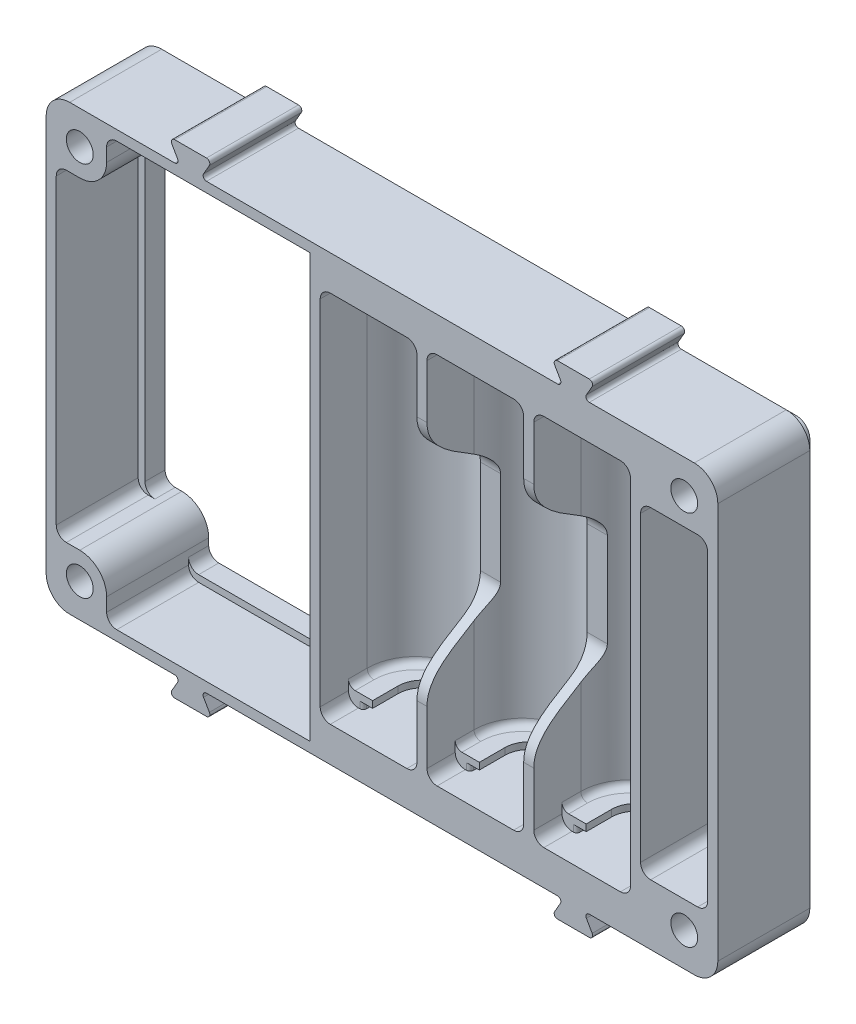
SolidWorks part; units mm, degrees
material "ABS"
ref_plane "Front Plane" through (0, 0, 0) normal (0, 0, 1) x (1, 0, 0)
ref_plane "Top Plane" through (0, 0, 0) normal (0, 1, 0) x (1, 0, 0)
ref_plane "Right Plane" through (0, 0, 0) normal (1, 0, 0) x (0, 0, -1)
sketch "Sketch1" plane through (0, 0, 0) normal (0, 1, 0) x (1, 0, 0)
  line L0 (-24.6, 0) -> (24.6, 0)
  line L1 (0, 0) -> (0, -8.2) construction
  line L2 (-5.4908, -1) -> (5.6475, -1) construction
  line L3 (7, -12.213) -> (7, -2.6204) construction
  line L4 (8.9, -12.0066) -> (8.9, -2.0587) construction
  line L5 (0, -8.2) -> (15.9, -8.2) construction
  line L6 (7.2, -8.2) -> (7.2, -15.2)
  line L7 (8.7, -8.2) -> (8.7, -15.2)
  line L8 (8.7, -15.2) -> (23.1, -15.2) construction
  line L9 (8.7, -15.2) -> (7.2, -15.2)
  line L10 (-1.7094, -15.2) -> (7.2, -15.2) construction
  line L11 (15.9, -8.2) -> (23.1, -8.2) construction
  line L12 (23.1, -15.2) -> (23.1, -8.2)
  line L13 (23.1, -15.2) -> (24.6, -15.2)
  line L14 (24.6, -15.2) -> (24.6, 0)
  line L15 (-24.6, -15.2) -> (-24.6, 0)
  line L16 (-23.1, -15.2) -> (-24.6, -15.2)
  line L17 (-23.1, -15.2) -> (-23.1, -8.2)
  line L18 (-8.7, -8.2) -> (-8.7, -15.2)
  line L19 (-8.7, -15.2) -> (-7.2, -15.2)
  line L20 (-7.2, -8.2) -> (-7.2, -15.2)
  circle A0 centre (0, -8.2) radius 7 construction
  arc A1 (-7.2, -8.2) -> (7.2, -8.2) centre (0, -8.2) cw
  circle A2 centre (15.9, -8.2) radius 7 construction
  arc A3 (8.7, -8.2) -> (23.1, -8.2) centre (15.9, -8.2) cw
  arc A4 (-8.7, -8.2) -> (-23.1, -8.2) centre (-15.9, -8.2) ccw
  dimension "D1" = 14
  dimension "D2" = 0.2
  dimension "D3" = 1
  dimension "D4" = 1.5
  dimension "D5" = 15.2
  dimension "D6" = 15.9
extrude "Boss-Extrude1" add sketch "Sketch1" along normal blind 27.8
sketch "Sketch2" plane through (0, 27.8, 0) normal (0, -1, 0) x (1, 0, 0)
  line L1 (-24.6, 15.2) -> (24.6, 15.2)
  line L2 (-24.6, 15.2) -> (-24.6, 0)
  line L3 (-24.6, 0) -> (24.6, 0)
  line L4 (24.6, 15.2) -> (24.6, 0)
extrude "Boss-Extrude2" add sketch "Sketch2" against normal blind 1.5
ref_plane "Plane1" through (-15.9, 0, 0) normal (1, 0, 0) x (0, 0, -1)
ref_plane "Plane3" through (15.9, 0, 0) normal (1, 0, 0) x (0, 0, -1)
sketch "Sketch6" plane through (0, 0, 0) normal (1, 0, 0) x (0, 0, -1)
  line L0 (-5, 0) -> (-15.2, 0)
  line L1 (-15.2, 0) -> (0, 0) construction
  line L2 (-15.2, 0) -> (-15.2, 18.3)
  line L3 (-15.2, 29.3) -> (-15.2, 0) construction
  line L4 (-5, 0) -> (-5, 7)
  line L5 (0, 29.3) -> (0, 0) construction
  line L6 (0, 29.3) -> (-15.2, 29.3) construction
  spline S0 degree 3 poles (-15.2, 18.3) (-15.2, 12.3) (-5, 11) (-5, 7) knots 0 0 0 0 1 1 1 1
  dimension "D4" = 12
  dimension "D5" = 18
  dimension "D1" = 7
  dimension "D2" = 5
  dimension "D3" = 11
extrude "Cut-Extrude2" cut sketch "Sketch6" against normal blind 15 and the other way blind 15
sketch "Sketch3" plane through (0, 27.8, 0) normal (0, -1, 0) x (1, 0, 0)
  line L0 (-10.4, 11) -> (-8.7, 11)
  line L1 (-8.7, 8.2) -> (-8.7, 15.2) construction
  line L2 (-8.7, 11) -> (-8.7, 0)
  line L3 (24.6, 0) -> (-24.6, 0) construction
  line L4 (-8.7, 0) -> (-23.1, 0)
  line L6 (-20.4, 2.9) -> (-11.4, 2.9)
  line L7 (-10.9, 3.4) -> (-10.9, 10.5)
  line L8 (-15.9, 15.2) -> (-15.9, 0) construction
  line L9 (-8.7, 15.2) -> (-23.1, 15.2) construction
  line L19 (-23.1, 11) -> (-23.1, 0)
  line L20 (-21.4, 11) -> (-23.1, 11)
  line L21 (-20.9, 3.4) -> (-20.9, 10.5)
  arc A1 (-11.4, 2.9) -> (-10.9, 3.4) centre (-11.4, 3.4) ccw
  arc A4 (-10.4, 11) -> (-10.9, 10.5) centre (-10.4, 10.5) ccw
  arc A6 (-20.4, 2.9) -> (-20.9, 3.4) centre (-20.4, 3.4) cw
  arc A7 (-21.4, 11) -> (-20.9, 10.5) centre (-21.4, 10.5) cw
  dimension "D6" = 0.5
  dimension "D7" = 0.5
  dimension "D1" = 5
  dimension "D2" = 11
  dimension "D3" = 2.9
extrude "Inner" add sketch "Sketch3" along normal blind 1
sketch "Sketch4" plane through (0, 26.8, 0) normal (0, -1, 0) x (1, 0, 0)
  line L1 (-8.7, 8.2) -> (-8.7, 15.2) construction
  line L2 (-8.7, 11) -> (-8.7, 0)
  line L3 (24.6, 0) -> (-24.6, 0) construction
  line L4 (-8.7, 0) -> (-23.1, 0)
  line L5 (-23.1, 0) -> (-23.1, 11)
  line L6 (-8.7, 11) -> (-10.4, 11) construction
  line L7 (-23.1, 11) -> (-19.5, 11)
  line L8 (-19.5, 11) -> (-19.5, 7.2)
  line L10 (-12.3, 7.2) -> (-12.3, 11)
  line L11 (-12.3, 11) -> (-8.7, 11)
  arc A0 (-19.5, 7.2) -> (-12.3, 7.2) centre (-15.9, 7.2) ccw
  dimension "D1" = 3.6
  dimension "D2" = 3.8
extrude "Boss-Extrude4" add sketch "Sketch4" along normal blind 1
sketch "Sketch5" plane through (0, 0, 15.2) normal (0, 0, 1) x (1, 0, 0)
  line L0 (-8.7, 27.8) -> (-23.1, 27.8) construction
  line L1 (-17.6, 27.8) -> (-14.2, 27.8)
  line L2 (-17.6, 27.8) -> (-17.6, 27.3)
  line L3 (-17.6, 27.3) -> (-14.2, 27.3)
  line L4 (-14.2, 27.8) -> (-14.2, 27.3)
  point P10 (-15.9, 27.8)
  dimension "D1" = 0.5
  dimension "D2" = 3.4
extrude "Cut-Extrude1" cut sketch "Sketch5" against normal through all
sketch "Sketch10" plane through (0, 0, 0) normal (0, 0, 1) x (1, 0, 0)
  line L0 (-24.6, 29.3) -> (24.6, 29.3) construction
  line L1 (-14.2, 27.3) -> (-17.6, 27.3)
  line L2 (-14.2, 27.3) -> (-14.2, 29.3)
  line L3 (-14.2, 29.3) -> (-17.6, 29.3)
  line L4 (-17.6, 27.3) -> (-17.6, 29.3)
extrude "Cut-Extrude6" cut sketch "Sketch10" along normal blind 0.6
mirror "Mirror1" about plane through (0, 0, 0) normal (1, 0, 0) of "Cut-Extrude6", "Inner", "Boss-Extrude4", "Cut-Extrude1"
ref_plane "Plane2" through (-7.95, 0, 0) normal (1, 0, 0) x (0, 0, -1)
mirror "Mirror2" about plane through (-7.95, 0, 0) normal (1, 0, 0) of "Cut-Extrude6", "Inner", "Boss-Extrude4", "Cut-Extrude1"
fillet "Fillet2" radius 1.5 6 edges at (-8.7, 27.8, 13.1) (-23.1, 27.8, 13.1) (8.7, 27.8, 13.1) (23.1, 27.8, 13.1) (7.2, 27.8, 13.1) (-7.2, 27.8, 13.1)
fillet "Fillet3" radius 1 9 edges at (-8.7, 25.8, 9.6) (-15.9, 25.8, 1) (-23.1, 25.8, 9.6) (23.1, 25.8, 9.6) (8.7, 25.8, 9.6) (7.2, 25.8, 9.6) (-7.2, 25.8, 9.6) (15.9, 25.8, 1) (0, 25.8, 1)
mirror "Mirror4" about plane through (0, 0, 0) normal (0, 1, 0) of bodies 108 110
sketch "Эскиз1" plane through (0, 0, 0) normal (0, 0, -1) x (-1, 0, 0)
  line L0 (-24.6, 29.3) -> (-24.6, -29.3) construction
  line L5 (-36.1, 33) -> (63.9, 33)
  line L6 (-36.1, 33) -> (-36.1, -33)
  line L7 (-36.1, -33) -> (63.9, -33)
  line L8 (63.9, 33) -> (63.9, -33)
  line L9 (-36.1, 33) -> (63.9, -33) construction
  line L10 (-36.1, -33) -> (63.9, 33) construction
  line L11 (-34.6, -31.5) -> (62.4, -31.5)
  line L12 (-34.6, -31.5) -> (-34.6, 31.5)
  line L13 (-34.6, 31.5) -> (62.4, 31.5)
  line L14 (62.4, -31.5) -> (62.4, 31.5)
  line L15 (-34.6, -31.5) -> (62.4, 31.5) construction
  line L16 (-34.6, 31.5) -> (62.4, -31.5) construction
  line L17 (24.6, 29.3) -> (24.6, -29.3) construction
  line L18 (-24.6, 29.3) -> (24.6, 29.3)
  line L19 (-24.6, 29.3) -> (-24.6, 31.5)
  line L20 (-24.6, 31.5) -> (24.6, 31.5)
  line L21 (24.6, 29.3) -> (24.6, 31.5)
  line L22 (-24.6, -29.3) -> (24.6, -29.3)
  line L23 (-24.6, -29.3) -> (-24.6, -31.5)
  line L24 (-24.6, -31.5) -> (24.6, -31.5)
  line L25 (24.6, -29.3) -> (24.6, -31.5)
  line L27 (-24.6, 29.3) -> (-24.6, -29.3) construction
  line L28 (62.4, 31.5) -> (54.9, 31.5)
  line L29 (62.4, 31.5) -> (62.4, 24)
  line L30 (62.4, 24) -> (54.9, 24)
  line L31 (54.9, 31.5) -> (54.9, 24)
  line L32 (62.4, -31.5) -> (54.9, -31.5)
  line L33 (62.4, -31.5) -> (62.4, -24)
  line L34 (62.4, -24) -> (54.9, -24)
  line L35 (54.9, -31.5) -> (54.9, -24)
  line L36 (-34.6, 31.5) -> (-24.6, 31.5)
  line L37 (-34.6, 31.5) -> (-34.6, 24)
  line L38 (-34.6, 24) -> (-24.6, 24)
  line L39 (-24.6, 31.5) -> (-24.6, 24)
  line L41 (-34.6, -31.5) -> (-24.6, -31.5)
  line L42 (-34.6, -31.5) -> (-34.6, -24)
  line L43 (-34.6, -24) -> (-24.6, -24)
  line L44 (-24.6, -31.5) -> (-24.6, -24)
  point P0 (13.9, 0)
  point P5 (13.9, 0)
  line M16 (24.6, 29.3) -> (17.6, 29.3)
  line M20 (14.2, 29.3) -> (1.7, 29.3)
  line M24 (-1.7, 29.3) -> (-14.2, 29.3)
  line M28 (-17.6, 29.3) -> (-24.6, 29.3)
  line M30 (-24.6, 29.3) -> (-24.6, -29.3)
  dimension "D1" = 100
  dimension "D2" = 66
  dimension "D3" = 1.5
  dimension "D4" = 1.5
  dimension "D5" = 10
  dimension "D6" = 7.5
extrude "Бобышка-Вытянуть1" add sketch "Эскиз1" against normal up to surface (15.2 mm away) contours L13 L31 L30 L14 | L35 L11 L14 L34 | L43 L12 L11 L23 M30 | L12 L38 L19 L13 M30 | L8 L5 L6 L7 L14 L11 L12 L13 | L21 L13 L19 L18 M16 M28 M24 M20 | L23 L22 L25 L24 region at (-13.9, 31.8018, 0) region at (29.6, -27.75, 0) region at (29.6, 27.75, 0) region at (-58.65, -27.75, 0) region at (0, 30.4, 0) region at (-58.65, 27.75, 0) up to face at (0, 0, 15.2)
sketch "Эскиз2" plane through (0, 0, 0) normal (0, 0, -1) x (-1, 0, 0)
  line L0 (62.4, -24) -> (62.4, 24) construction
  line L1 (-34.6, -31.5) -> (62.4, -31.5)
  line L2 (-34.6, -31.5) -> (-34.6, 31.5)
  line L3 (-34.6, 31.5) -> (62.4, 31.5)
  line L4 (62.4, -31.5) -> (62.4, 31.5)
  line L5 (-34.6, -24) -> (-34.6, 24) construction
  line L6 (24.6, 31.5) -> (54.9, 31.5) construction
  line L7 (24.6, -31.5) -> (54.9, -31.5) construction
  line L8 (-24.6, 24) -> (-24.6, -24) construction
  line L11 (-34.6, 24) -> (-24.6, 24)
  line L12 (-24.6, 31.5) -> (-24.6, 24)
  line L13 (54.9, 24) -> (62.4, 24)
  line L14 (54.9, 24) -> (54.9, 31.5)
  line L17 (54.9, -24) -> (62.4, -24)
  line L18 (54.9, -24) -> (54.9, -31.5)
  line L23 (-34.6, -24) -> (-24.6, -24)
  line L24 (-24.6, -31.5) -> (-24.6, -24)
  line L25 (-24.6, 30.5) -> (54.9, 30.5)
  line L26 (-24.6, -30.5) -> (54.9, -30.5)
  line L27 (-33.6, 24) -> (-33.6, -24)
  line L28 (61.4, -24) -> (61.4, 24)
  line L29 (62.4, 24) -> (54.9, 24) construction
  line M25 (-34.6, 24) -> (-24.6, 24)
  line M27 (-24.6, -24) -> (-34.6, -24)
  line M28 (-34.6, -24) -> (-34.6, 24)
  line M29 (24.6, -31.5) -> (24.6, 31.5)
  line M30 (24.6, 31.5) -> (54.9, 31.5)
  line M31 (54.9, 31.5) -> (54.9, 24)
  line M32 (54.9, 24) -> (62.4, 24)
  line M33 (62.4, 24) -> (62.4, -24)
  line M34 (62.4, -24) -> (54.9, -24)
  line M35 (54.9, -24) -> (54.9, -31.5)
  line M36 (54.9, -31.5) -> (24.6, -31.5)
  dimension "D1" = 1
  dimension "D2" = 1
  dimension "D3" = 1
  dimension "D4" = 1
extrude "Бобышка-Вытянуть2" add sketch "Эскиз2" against normal blind 3 contours L12 L3 L2 L11 M25 | L12 L25 L3 M29 | L25 M29 M31 M30 | L13 L4 L3 L14 M32 M31 | L28 L13 M34 M33 | L1 L4 L17 L18 M34 M35 | L26 L18 M29 M36 | L26 L24 L1 M29 | L1 L24 L23 L2 M27 | L27 L23 M25 M28 region at (29.6, -27.75, 0) region at (0, -31, 0) region at (34.1, 0, 0) region at (-39.75, -31, 0) region at (29.6, 27.75, 0) region at (-58.65, -27.75, 0) region at (-39.75, 31, 0) region at (0, 31, 0) region at (-61.9, 0, 0) region at (-58.65, 27.75, 0)
fillet "Скругление6" radius 3.5 4 edges at (36.1, 33, 7.6) (36.1, -33, 7.6) (-63.9, -33, 7.6) (-63.9, 33, 7.6)
sketch "Эскиз8" plane through (0, 0, 0) normal (0, 0, -1) x (-1, 0, 0)
  line L8 (62.4, -29.5) -> (62.4, 29.5)
  line L9 (-32.6, -31.5) -> (60.4, -31.5)
  line L10 (-34.6, 29.5) -> (-34.6, -29.5)
  line L11 (60.4, 31.5) -> (-32.6, 31.5)
  line L12 (62.4, -29.5) -> (62.4, 29.5)
  line L13 (-32.6, -31.5) -> (60.4, -31.5)
  line L14 (-34.6, 29.5) -> (-34.6, -29.5)
  line L15 (60.4, 31.5) -> (-32.6, 31.5)
  line L20 (63.9, -29.5) -> (63.9, 29.5)
  line L21 (-32.6, -33) -> (60.4, -33)
  line L22 (-36.1, 29.5) -> (-36.1, -29.5)
  line L23 (60.4, 33) -> (-32.6, 33)
  line L24 (63.9, -29.5) -> (63.9, 29.5)
  line L25 (-32.6, -33) -> (60.4, -33)
  line L26 (-36.1, 29.5) -> (-36.1, -29.5)
  line L27 (60.4, 33) -> (-32.6, 33)
  arc A8 (62.4, 29.5) -> (60.4, 31.5) centre (60.4, 29.5) ccw
  arc A9 (60.4, -31.5) -> (62.4, -29.5) centre (60.4, -29.5) ccw
  arc A10 (-34.6, -29.5) -> (-32.6, -31.5) centre (-32.6, -29.5) ccw
  arc A11 (-32.6, 31.5) -> (-34.6, 29.5) centre (-32.6, 29.5) ccw
  arc A12 (62.4, 29.5) -> (60.4, 31.5) centre (60.4, 29.5) ccw
  arc A13 (60.4, -31.5) -> (62.4, -29.5) centre (60.4, -29.5) ccw
  arc A14 (-34.6, -29.5) -> (-32.6, -31.5) centre (-32.6, -29.5) ccw
  arc A15 (-32.6, 31.5) -> (-34.6, 29.5) centre (-32.6, 29.5) ccw
  arc A20 (63.9, 29.5) -> (60.4, 33) centre (60.4, 29.5) ccw
  arc A21 (60.4, -33) -> (63.9, -29.5) centre (60.4, -29.5) ccw
  arc A22 (-36.1, -29.5) -> (-32.6, -33) centre (-32.6, -29.5) ccw
  arc A23 (-32.6, 33) -> (-36.1, 29.5) centre (-32.6, 29.5) ccw
  arc A24 (63.9, 29.5) -> (60.4, 33) centre (60.4, 29.5) ccw
  arc A25 (60.4, -33) -> (63.9, -29.5) centre (60.4, -29.5) ccw
  arc A26 (-36.1, -29.5) -> (-32.6, -33) centre (-32.6, -29.5) ccw
  arc A27 (-32.6, 33) -> (-36.1, 29.5) centre (-32.6, 29.5) ccw
  dimension "D1" = 1.5
  dimension "D2" = 0
extrude "Вырез-Вытянуть1" cut sketch "Эскиз8" against normal blind 1.5
fillet "Скругление7" radius 1.5 10 edges at (-24.6, -30.5, 1.5) (-54.9, -30.5, 1.5) (-24.6, 30.5, 1.5) (-54.9, 30.5, 1.5) (-61.4, 24, 1.5) (-61.4, -24, 1.5) (33.6, -24, 1.5) (24.6, -24, 7.6) (24.6, 24, 7.6) (33.6, 24, 1.5)
sketch "Эскиз11" plane through (0, 0, 15.2) normal (0, 0, 1) x (1, 0, 0)
  line L0 (-43.9, 33) -> (-45.6321, 36)
  line L2 (-45.6321, 36) -> (-39.1679, 36)
  line L3 (-39.1679, 36) -> (-40.9, 33)
  line L4 (-40.9, 33) -> (-43.9, 33)
  line L5 (13.1, 33) -> (11.3679, 36)
  line L6 (11.3679, 36) -> (17.8321, 36)
  line L7 (17.8321, 36) -> (16.1, 33)
  line L8 (16.1, 33) -> (13.1, 33)
  line L11 (-43.9, -33) -> (-45.6321, -36)
  line L13 (-45.6321, -36) -> (-39.1679, -36)
  line L14 (-39.1679, -36) -> (-40.9, -33)
  line L15 (-40.9, -33) -> (-43.9, -33)
  line L16 (13.1, -33) -> (11.3679, -36)
  line L17 (11.3679, -36) -> (17.8321, -36)
  line L18 (17.8321, -36) -> (16.1, -33)
  line L19 (16.1, -33) -> (13.1, -33)
  line L20 (-60.4, -33) -> (32.6, -33) construction
  line L21 (-60.4, 33) -> (32.6, 33) construction
  line L22 (-63.9, -29.5) -> (-63.9, 29.5) construction
  line L23 (36.1, -29.5) -> (36.1, 29.5) construction
  dimension "D1" = 60
  dimension "D2" = 3
  dimension "D3" = 3
  dimension "D4" = 3
  dimension "D5" = 20
  dimension "D6" = 20
  dimension "D7" = 3
extrude "Бобышка-Вытянуть3" add sketch "Эскиз11" against normal up to surface (13.7 mm away) up to face at (-13.9, 0, 1.5)
fillet "Скругление8" radius 0.5 16 edges at (-45.6321, -36, 8.35) (-43.9, -33, 8.35) (-39.1679, -36, 8.35) (-40.9, -33, 8.35) (17.8321, -36, 8.35) (16.1, -33, 8.35) (11.3679, -36, 8.35) (13.1, -33, 8.35) (16.1, 33, 8.35) (17.8321, 36, 8.35) (13.1, 33, 8.35) (11.3679, 36, 8.35) (-43.9, 33, 8.35) (-40.9, 33, 8.35) (-39.1679, 36, 8.35) (-45.6321, 36, 8.35)
fillet "Скругление9" radius 1.5 6 edges at (34.6, 24, 9.1) (34.6, -24, 9.1) (-54.9, 31.5, 9.1) (-62.4, 24, 9.1) (-62.4, -24, 9.1) (-54.9, -31.5, 9.1)
sketch "Эскиз3" plane through (0, 0, 15.2) normal (0, 0, 1) x (1, 0, 0)
  line L4 (-60.4, 33) -> (-44.766, 33) construction
  line L5 (-63.9, -29.5) -> (-63.9, 29.5) construction
  line L6 (36.1, -29.5) -> (36.1, 29.5) construction
  line L7 (-60.4, -33) -> (-44.766, -33) construction
  circle A0 centre (-58.9, 28) radius 2
  circle A1 centre (31.1, 28) radius 2
  circle A2 centre (31.1, -28) radius 2
  circle A3 centre (-58.9, -28) radius 2
  point P0 (-58.9, 28)
  point P1 (31.1, 28)
  point P2 (31.1, -28)
  point P3 (-58.9, -28)
  dimension "D5" = 4
  dimension "D1" = 5
  dimension "D2" = 5
  dimension "D3" = 5
  dimension "D4" = 5
sketch "Эскиз12" plane through (0, 0, 0) normal (0, 0, -1) x (-1, 0, 0)
  circle A0 centre (-31.1, 28) radius 2
  circle A1 centre (58.9, 28) radius 2
  circle A2 centre (58.9, -28) radius 2
  circle A3 centre (-31.1, -28) radius 2
  point P8 (58.9, 28)
  point P9 (58.9, -28)
  point P10 (-31.1, -28)
  point P12 (-31.1, 28)
  dimension "D1" = 4
extrude "Вырез-Вытянуть2" cut sketch "Эскиз12" against normal blind 4.2
extrude "Вырез-Вытянуть3" cut sketch "Эскиз3" against normal blind 4.2
fillet "Скругление10" radius 4 2 edges at (-54.9, 24, 7.6) (-54.9, -24, 7.6)
